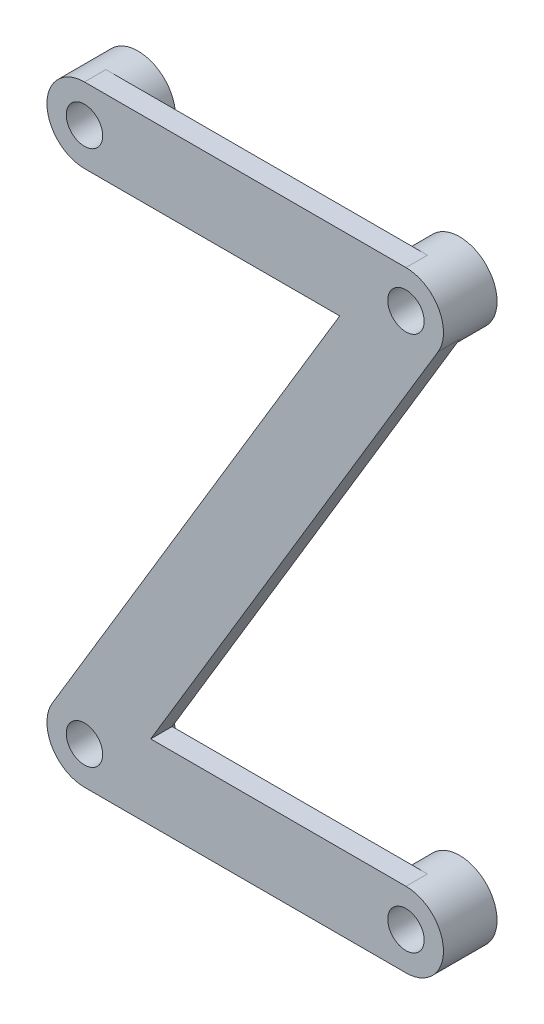
SolidWorks part; units mm, degrees
ref_plane "Спереди" through (0, 0, 0) normal (0, 0, 1) x (1, 0, 0)
ref_plane "Сверху" through (0, 0, 0) normal (0, 1, 0) x (1, 0, 0)
ref_plane "Справа" through (0, 0, 0) normal (1, 0, 0) x (0, 0, -1)
sketch "Эскиз1" plane through (0, 0, 0) normal (0, 0, 1) x (1, 0, 0)
  line L10 (-15, 28.5) -> (15, 28.5)
  line L11 (-15, 25) -> (15, 25) construction
  line L12 (-15, 25) -> (-15, -25) construction
  line L13 (-15, -25) -> (15, -25) construction
  line L14 (15, 25) -> (15, -25) construction
  line L15 (-15, 25) -> (15, -25) construction
  line L16 (-15, -25) -> (15, 25) construction
  line L17 (-15, 21.5) -> (8.8183, 21.5)
  line L18 (-8.8183, -21.5) -> (15, -21.5)
  line L19 (18.0012, 23.1993) -> (-8.8183, -21.5)
  line L21 (-15, -28.5) -> (15, -28.5)
  line L22 (8.8183, 21.5) -> (-18.0012, -23.1993)
  circle A8 centre (15, 25) radius 3.5
  circle A9 centre (15, -25) radius 3.5
  circle A10 centre (-15, -25) radius 3.5
  circle A11 centre (-15, 25) radius 3.5
  circle A12 centre (-15, 25) radius 1.7
  circle A13 centre (15, 25) radius 1.7
  circle A14 centre (-15, -25) radius 1.7
  circle A15 centre (15, -25) radius 1.7
  point P18 (0, 0)
  dimension "D6" = 7
  dimension "D1" = 3.4
  dimension "D4" = 30
  dimension "D5" = 50
extrude "Основа" add sketch "Эскиз1" against normal blind 2 contours A11 L17 L22 A10 L21 A9 L18 L19 A8 L10 region at (0, 0, 0)
extrude "Стойки" add sketch "Эскиз1<3>" against normal blind 5 contours A11 | A8 | A10 | A9 region at (-12.5951, 27.4049, 0) region at (17.4049, 27.4049, 0) region at (-14.0922, -21.7224, 0) region at (17.4049, -22.5951, 0)
sketch "Эскиз1<3>" plane through (0, 0, 0) normal (0, 0, 1) x (1, 0, 0) same geometry as "Эскиз1"
